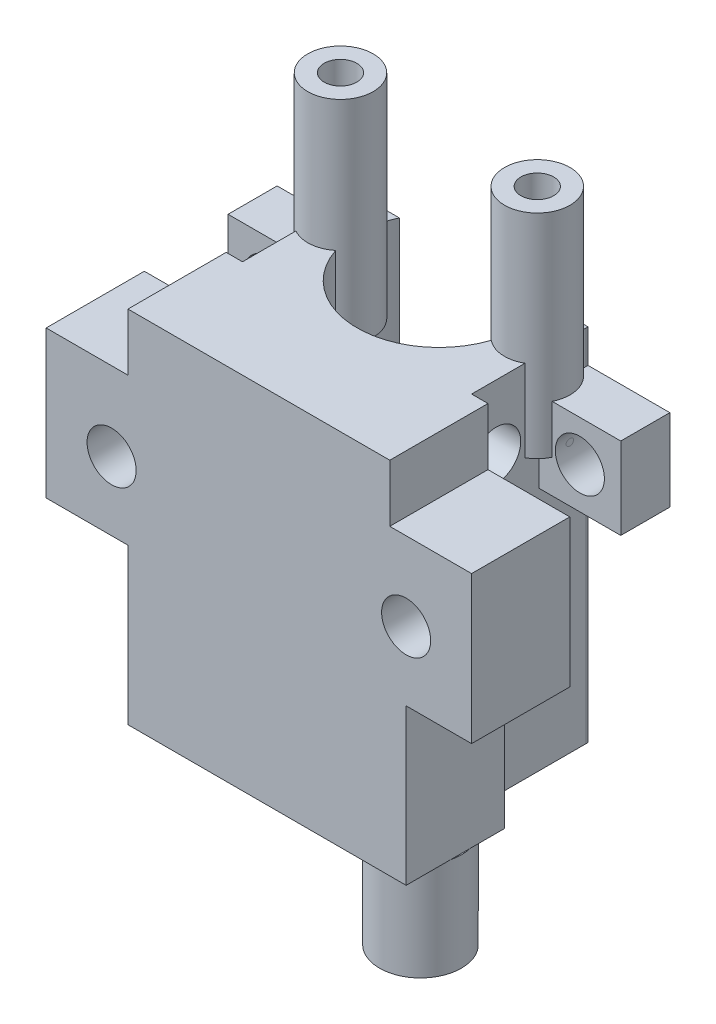
SolidWorks part; units mm, degrees
ref_plane "Plano frontal" through (0, 0, 0) normal (0, 0, 1) x (1, 0, 0)
ref_plane "Plano superior" through (0, 0, 0) normal (0, 1, 0) x (1, 0, 0)
ref_plane "Plano direito" through (0, 0, 0) normal (1, 0, 0) x (0, 0, -1)
sketch "Esboço1" plane through (0, 0, 0) normal (0, 0, 1) x (1, 0, 0)
  line L0 (-10.6371, -1.8328) -> (6.3629, -1.8328)
  line L7 (-10.6371, 20.1672) -> (5.3629, 20.1672)
  line L8 (5.3629, 16.6672) -> (10.3629, 16.6672)
  line L9 (10.3629, 16.6672) -> (10.3629, 7.6672)
  line L10 (10.3629, 7.6672) -> (6.3629, 7.6672)
  line L11 (-10.6371, 7.6672) -> (-10.6371, -1.8328)
  line L12 (-10.6371, 16.6672) -> (-15.6371, 16.6672)
  line L13 (-15.6371, 16.6672) -> (-15.6371, 7.6672)
  line L14 (-15.6371, 7.6672) -> (-10.6371, 7.6672)
  line L15 (6.3629, -1.8328) -> (6.3629, 7.6672)
  line L16 (5.3629, 16.6672) -> (5.3629, 20.1672)
  line L17 (-10.6371, 16.6672) -> (-10.6371, 20.1672)
  circle A1 centre (6.3629, 11.8672) radius 1.5
  circle A2 centre (-11.6371, 11.8672) radius 1.5
  dimension "D10" = 3
  dimension "D12" = 3
  dimension "D4" = 17
  dimension "D6" = 22
  dimension "D8" = 16
  dimension "D13" = 4
  dimension "D15" = 3.5
  dimension "D16" = 5
  dimension "D17" = 9
  dimension "D18" = 3.5
  dimension "D19" = 5
  dimension "D20" = 9
  dimension "D21" = 4
  dimension "D22" = 4.2
  dimension "D23" = 4.2
extrude "Ressalto-extrusão1" add sketch "Esboço1" along normal blind 6
sketch "Esboço6" plane through (0, 0, 0) normal (0, 0, -1) x (-1, 0, 0)
  line L0 (-5.3629, 20.1672) -> (10.6371, 20.1672) construction
  line L1 (-4.3629, 20.1672) -> (9.6371, 20.1672)
  line L2 (-4.3629, 20.1672) -> (-4.3629, -1.8328)
  line L3 (-4.3629, -1.8328) -> (9.6371, -1.8328)
  line L4 (9.6371, 20.1672) -> (9.6371, -1.8328)
  line L5 (10.6371, -1.8328) -> (-6.3629, -1.8328) construction
  line L6 (10.6371, 9.6672) -> (10.6371, -1.8328) construction
  line L7 (-5.3629, 7.1672) -> (-5.3629, 7.6672) construction
  dimension "D1" = 1
  dimension "D2" = 1
extrude "Ressalto-extrusão3" add sketch "Esboço6" along normal blind 12
sketch "Esboço7" plane through (0, -1.8328, 0) normal (0, -1, 0) x (1, 0, 0)
  line L0 (4.3629, 0) -> (-9.6371, 0)
  line L1 (-2.6371, 0) -> (-2.6371, -5)
  circle A0 centre (-2.6371, -5) radius 5
  dimension "D1" = 5
extrude "Corte-extrusão4" cut sketch "Esboço7" against normal through all
fillet "Filete3" radius 5 2 edges at (-9.6371, 9.1672, -12) (4.3629, 9.1672, -12)
sketch "Esboço8" plane through (0, -1.8328, 0) normal (0, -1, 0) x (-1, 0, 0)
  line L0 (2.6371, 5) -> (2.6371, -2.7)
  line L1 (2.6371, -2.7) -> (-3.9389, -2.7)
  dimension "D1" = 7.7
  dimension "D2" = 6.576
  dimension "D3" = 10.1259
sketch "Esboço11" plane through (0, -1.8328, 0) normal (0, -1, 0) x (1, 0, 0)
  circle A0 centre (3.9389, 2.7) radius 2.5
  dimension "D1" = 5
extrude "Ressalto-extrusão11" add sketch "Esboço11" along normal blind 6
sketch "Esboço15" plane through (0, 20.1672, 0) normal (0, 1, 0) x (1, 0, 0)
  line L0 (-7.6638, 5) -> (-9.6371, 5)
  line L1 (-9.6371, 7) -> (-9.6371, 0) construction
  line L2 (2.3895, 5) -> (4.3629, 5)
  line L3 (4.3629, 7) -> (4.3629, 0) construction
  circle A2 centre (-8.6505, 5) radius 2
  circle A3 centre (3.3762, 5) radius 2
  dimension "D1" = 4
  dimension "D2" = 4
extrude "Ressalto-extrusão13" add sketch "Esboço15" along normal blind 8 and the other way blind 5
sketch "Esboço17" plane through (0, 28.1672, 0) normal (0, 1, 0) x (1, 0, 0)
  circle A0 centre (-8.6505, 5) radius 1
  circle A1 centre (3.3762, 5) radius 1
  dimension "D1" = 2
  dimension "D2" = 2
extrude "Corte-extrusão6" cut sketch "Esboço17" against normal blind 8 contours A0 | A1
sketch "Esboço20" plane through (0, -7.8328, 0) normal (0, -1, 0) x (1, 0, 0)
  circle A0 centre (3.9389, 2.7) radius 0.75
  dimension "D1" = 1.5
extrude "Corte-extrusão7" cut sketch "Esboço20" against normal blind 5
sketch3d "3DSketch4"
  line L0 (-9.6371, -1.8328, 0) -> (-9.6371, 20.1672, 0) construction
  point P0 (-9.6371, 8.771, 0)
ref_plane "Plano4" through (0, 0, -7.1152) normal (0, 0, -1) x (1, 0, 0)
sketch "Esboço21" plane through (0, 0, -7.1152) normal (0, 0, -1) x (1, 0, 0)
  line L1 (8.5566, 5.7142) -> (-14.1129, 5.7142)
  line L2 (8.5566, 5.7142) -> (8.5566, -25.4431)
  line L3 (8.5566, -25.4431) -> (-14.1129, -25.4431)
  line L4 (-14.1129, 5.7142) -> (-14.1129, -25.4431)
extrude "Corte-extrusão8" cut sketch "Esboço21" along normal blind 6
sketch "Esboço22" plane through (0, 0, -7.1152) normal (0, 0, -1) x (1, 0, 0)
  line L0 (-9.6358, 1.8328) -> (-9.6358, -20.1672) construction
  line L1 (-9.6358, -18.1259) -> (-14.6358, -18.1259)
  line L2 (-9.6358, -18.1259) -> (-9.6358, -13.1259)
  line L3 (-9.6358, -13.1259) -> (-14.6358, -13.1259)
  line L4 (-14.6358, -18.1259) -> (-14.6358, -13.1259)
  line L5 (-9.6358, -13.1259) -> (4.3629, -13.1259)
  line L6 (4.3629, -20.1672) -> (4.3629, -15.1672) construction
  line L8 (4.3629, -13.1259) -> (9.3629, -13.1259)
  line L9 (4.3629, -13.1259) -> (4.3629, -18.1259)
  line L10 (4.3629, -18.1259) -> (9.3629, -18.1259)
  line L11 (9.3629, -13.1259) -> (9.3629, -18.1259)
  circle A1 centre (-12.1358, -15.6259) radius 1.5
  circle A2 centre (6.8629, -15.6259) radius 1.5
  dimension "D3" = 3
  dimension "D6" = 3
  dimension "D1" = 5
  dimension "D2" = 5
  dimension "D4" = 5
  dimension "D5" = 5
extrude "Ressalto-extrusão15" add sketch "Esboço22" against normal blind 3 contours L4 L1 L2 L3 A1 | L11 L8 L9 L10 A2
chamfer "Chanfro5" distance 1 angle 45 2 edges at (7.8629, 11.8672, 0) (-10.1371, 11.8672, 0)
sketch "Esboço23" plane through (-9.6371, 0, 0) normal (-1, 0, 0) x (0, 0, 1)
  line L0 (-3.2603, 20.1672) -> (0, 20.1672) construction
  line L1 (6, 16.6672) -> (6, 7.6672) construction
  circle A0 centre (-1.5, 16.1672) radius 1.5
  dimension "D1" = 3
  dimension "D2" = 4
  dimension "D3" = 7.5
extrude "Corte-extrusão9" cut sketch "Esboço23" against normal blind 17
